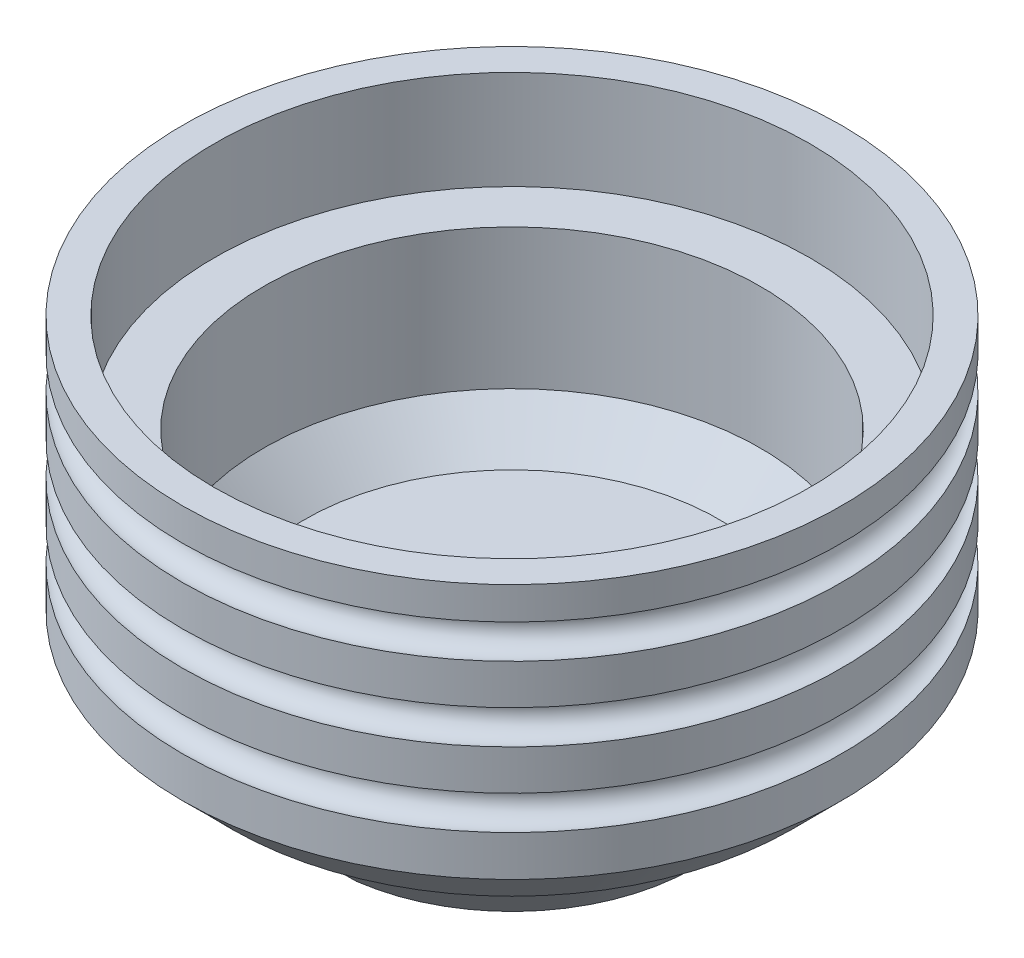
SolidWorks part; units mm, degrees
material "ABS PC"
ref_plane "正面" through (0, 0, 0) normal (0, 0, 1) x (1, 0, 0)
ref_plane "平面" through (0, 0, 0) normal (0, 1, 0) x (1, 0, 0)
ref_plane "右側面" through (0, 0, 0) normal (1, 0, 0) x (0, 0, -1)
sketch "ｽｹｯﾁ2" plane through (0, 0, 0) normal (1, 0, 0) x (0, 0, -1)
  line L0 (4, -2) -> (4, -27.3) construction
  line L1 (-1.125, -19) -> (-1.125, -6)
  line L2 (-1.125, -6) -> (-26.15, -6)
  line L3 (-26.15, -6) -> (-26.15, 16)
  line L4 (-26.15, 16) -> (-32.15, 16)
  line L5 (-32.15, 16) -> (-32.15, 28)
  line L6 (-32.15, 28) -> (-36, 28)
  line L7 (-36, 28) -> (-36, -9)
  line L14 (-36, -9) -> (-16.125, -9)
  line L16 (-1, -2) -> (9, -2) construction
  line L17 (-9.15, -3) -> (17.15, -3) construction
  line L19 (-1.125, -19) -> (-16.125, -19)
  line L20 (-16.125, -19) -> (-16.125, -9)
  line L21 (-35.5, 13) -> (-26.15, 13) construction
  line L22 (-35.5, 28) -> (-35.5, -9) construction
  circle A0 centre (-35.5, 22) radius 2.125
  circle A2 centre (-35.5, 13) radius 2.125
  circle A3 centre (-35.5, 4) radius 2.125
  dimension "D11" = 4.25
  dimension "D1" = 10.25
  dimension "D2" = 37
  dimension "D3" = 15
  dimension "D4" = 3
  dimension "D5" = 80
  dimension "D6" = 72.3
  dimension "D7" = 6
  dimension "D8" = 12
  dimension "2" = 3
  dimension "D9" = 10
  dimension "D10" = 15
  dimension "D12" = 0.5
  dimension "D13" = 9
revolve "回転1" add sketch "ｽｹｯﾁ2" angle 360 about L0 region at (0, -18.4147, 8.625)
chamfer "面取り1" distance 5 angle 45 1 edges at (0, -6, 26.15)
sketch "ｽｹｯﾁ3" plane through (0, -19, 0) normal (0, -1, 0) x (1, 0, 0)
  line L1 (-3.075, 0.1) -> (3.075, 0.1)
  line L2 (-3, 0) -> (3, 0) construction
  circle A1 centre (0, -4) radius 5.125 construction
  circle A2 centre (0, -4) radius 5.125
  dimension "D1" = 0.1
extrude "ﾎﾞｽ - 押し出し1" add sketch "ｽｹｯﾁ3" against normal blind 11.5 contours L1 region at (0, -19, 0.5137)
chamfer "面取り2" distance 12 angle 45 1 edges at (0, -9, 16.125)
sketch "ｽｹｯﾁ4" plane through (0, 0, 0.1) normal (0, 0, -1) x (-1, 0, 0)
  line L0 (0, -18.5) -> (0, -15.5002) construction
  line L2 (-3, -14.0001) -> (3, -14.0001)
  line L3 (-3, -14.0001) -> (-3, -20.0001)
  line L4 (-3, -20.0001) -> (3, -20.0001)
  line L5 (3, -14.0001) -> (3, -20.0001)
  line L6 (-3, -14.0001) -> (3, -20.0001) construction
  line L7 (-3, -20.0001) -> (3, -14.0001) construction
  spline S0 degree 3 poles (0, -18.5) (0.1532, -18.5) (0.3083, -18.4759) (0.4538, -18.4297) (0.6168, -18.378) (0.7722, -18.2971) (0.9074, -18.1944) (1.0388, -18.0946) (1.1548, -17.9715) (1.2466, -17.8343) (1.3352, -17.7019) (1.4036, -17.5529) (1.4462, -17.3983) (1.4893, -17.2418) (1.5069, -17.0752) (1.4975, -16.9127) (1.4876, -16.7431) (1.4478, -16.5729) (1.3822, -16.4173) (1.3163, -16.2609) (1.2224, -16.1145) (1.1087, -15.9897) (0.999, -15.8692) (0.8677, -15.7656) (0.7245, -15.6866) (0.5846, -15.6094) (0.4296, -15.5539) (0.2714, -15.5248) (0.1096, -15.495) (-0.06, -15.4922) (-0.2228, -15.5166) (-0.3916, -15.542) (-0.558, -15.5974) (-0.7075, -15.6773) (-0.8561, -15.7568) (-0.9924, -15.8627) (-1.1058, -15.9865) (-1.2147, -16.1053) (-1.3055, -16.2437) (-1.3711, -16.3917) (-1.4359, -16.5377) (-1.4778, -16.697) (-1.4932, -16.857) (-1.5091, -17.0229) (-1.4966, -17.1942) (-1.4572, -17.3558) (-1.4166, -17.5221) (-1.3463, -17.6829) (-1.2529, -17.8248) (-1.1614, -17.9637) (-1.0454, -18.0884) (-0.9137, -18.1896) (-0.7853, -18.2882) (-0.6385, -18.3671) (-0.4843, -18.4197) (-0.3299, -18.4723) (-0.1638, -18.5) (0, -18.5) (0.1532, -18.5) (0.3083, -18.4759) knots -0.0521 0 0 0 0.048635 0.048635 0.048635 0.10323 0.10323 0.10323 0.156231 0.156231 0.156231 0.207339 0.207339 0.207339 0.259122 0.259122 0.259122 0.313213 0.313213 0.313213 0.367545 0.367545 0.367545 0.419925 0.419925 0.419925 0.471108 0.471108 0.471108 0.523516 0.523516 0.523516 0.577917 0.577917 0.577917 0.631926 0.631926 0.631926 0.683723 0.683723 0.683723 0.734821 0.734821 0.734821 0.787892 0.787892 0.787892 0.842513 0.842513 0.842513 0.89589 0.89589 0.89589 0.9479 0.9479 0.9479 1 1 1 1.048635 1.048635 1.048635 only from (0, -18.5) to (0, -18.5) construction
  spline S1 degree 3 poles (0, -18.5) (0.1532, -18.5) (0.3083, -18.4759) (0.4538, -18.4297) (0.6168, -18.378) (0.7722, -18.2971) (0.9074, -18.1944) (1.0388, -18.0946) (1.1548, -17.9715) (1.2466, -17.8343) (1.3352, -17.7019) (1.4036, -17.5529) (1.4462, -17.3983) (1.4893, -17.2418) (1.5069, -17.0752) (1.4975, -16.9127) (1.4876, -16.7431) (1.4478, -16.5729) (1.3822, -16.4173) (1.3163, -16.2609) (1.2224, -16.1145) (1.1087, -15.9897) (0.999, -15.8692) (0.8677, -15.7656) (0.7245, -15.6866) (0.5846, -15.6094) (0.4296, -15.5539) (0.2714, -15.5248) (0.1096, -15.495) (-0.06, -15.4922) (-0.2228, -15.5166) (-0.3916, -15.542) (-0.558, -15.5974) (-0.7075, -15.6773) (-0.8561, -15.7568) (-0.9924, -15.8627) (-1.1058, -15.9865) (-1.2147, -16.1053) (-1.3055, -16.2437) (-1.3711, -16.3917) (-1.4359, -16.5377) (-1.4778, -16.697) (-1.4932, -16.857) (-1.5091, -17.0229) (-1.4966, -17.1942) (-1.4572, -17.3558) (-1.4166, -17.5221) (-1.3463, -17.6829) (-1.2529, -17.8248) (-1.1614, -17.9637) (-1.0454, -18.0884) (-0.9137, -18.1896) (-0.7853, -18.2882) (-0.6385, -18.3671) (-0.4843, -18.4197) (-0.3299, -18.4723) (-0.1638, -18.5) (0, -18.5) (0.1532, -18.5) (0.3083, -18.4759) knots -0.0521 0 0 0 0.048635 0.048635 0.048635 0.10323 0.10323 0.10323 0.156231 0.156231 0.156231 0.207339 0.207339 0.207339 0.259122 0.259122 0.259122 0.313213 0.313213 0.313213 0.367545 0.367545 0.367545 0.419925 0.419925 0.419925 0.471108 0.471108 0.471108 0.523516 0.523516 0.523516 0.577917 0.577917 0.577917 0.631926 0.631926 0.631926 0.683723 0.683723 0.683723 0.734821 0.734821 0.734821 0.787892 0.787892 0.787892 0.842513 0.842513 0.842513 0.89589 0.89589 0.89589 0.9479 0.9479 0.9479 1 1 1 1.048635 1.048635 1.048635 only from (0, -18.5) to (0, -18.5) construction
  point P1 (0, -17.0001)
  dimension "D1" = 6
  dimension "D2" = 6
extrude "ｶｯﾄ - 押し出し1" cut sketch "ｽｹｯﾁ4" against normal through all from offset 16 offset against normal yes
extrude "ｶｯﾄ - 押し出し2" cut sketch "ｽｹｯﾁ4<2>" along normal through all from offset 25
sketch "ｽｹｯﾁ4<2>" plane through (0, 0, 0.1) normal (0, 0, -1) x (-1, 0, 0) same geometry as "ｽｹｯﾁ4"
sketch "ｽｹｯﾁ5" plane through (0, 0, 16.1) normal (0, 0, 1) x (1, 0, 0)
  line L0 (0, -14.0001) -> (0, -17.0001) construction
  line L1 (-3, -14.0001) -> (3, -14.0001) construction
  circle A0 centre (0, -17.0001) radius 1.65
  dimension "D2" = 3.3
  dimension "D1" = 3
extrude "ｶｯﾄ - 押し出し3" cut sketch "ｽｹｯﾁ5" against normal through all
chamfer "面取り3" distance 6 angle 45 1 edges at (0, -9, 36)
